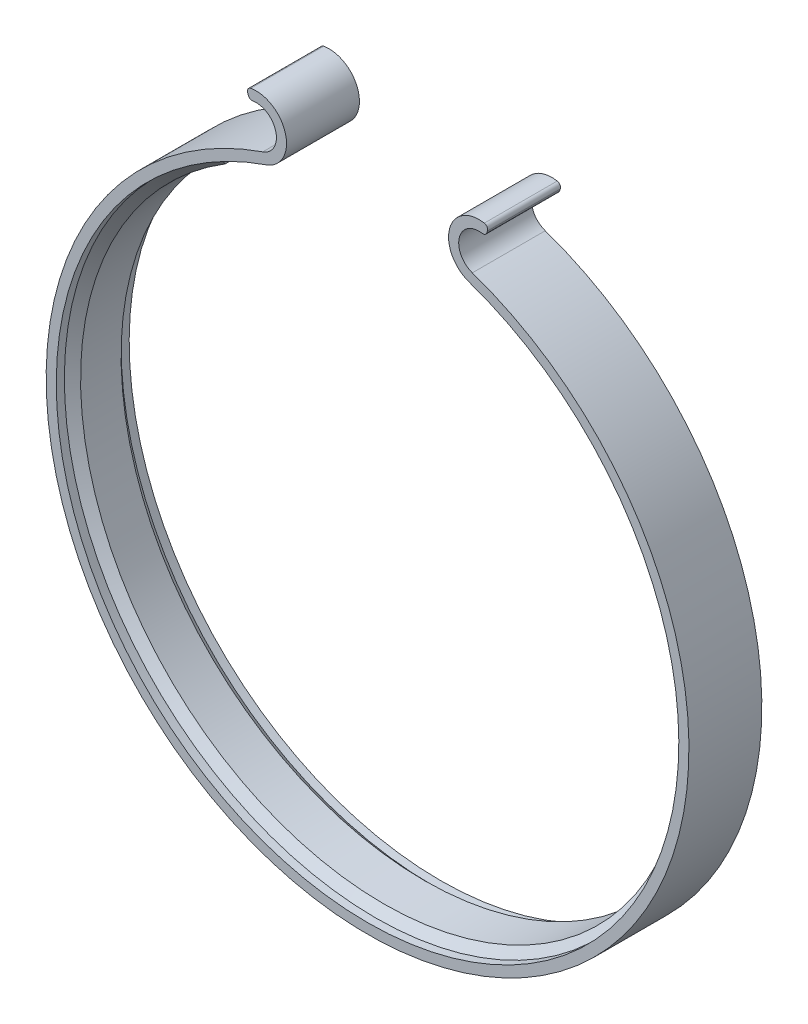
SolidWorks part; units mm, degrees
ref_plane "Front Plane" through (0, 0, 0) normal (0, 0, 1) x (1, 0, 0)
ref_plane "Top Plane" through (0, 0, 0) normal (0, 1, 0) x (1, 0, 0)
ref_plane "Right Plane" through (0, 0, 0) normal (1, 0, 0) x (0, 0, -1)
sketch "Sketch1" plane through (0, 0, 0) normal (0, 0, 1) x (1, 0, 0)
  line L0 (0, 0) -> (0, 98.4093) construction
  line L1 (29.4288, 85.3341) -> (29.5939, 85.813)
  line L3 (-29.4288, 85.3341) -> (-29.5939, 85.813)
  arc A0 (-25.0548, 72.6511) -> (25.0548, 72.6511) centre (0, 0) ccw
  arc A1 (-25.8699, 75.0145) -> (25.8699, 75.0145) centre (0, 0) ccw
  arc A2 (-25.8699, 75.0145) -> (-28.3195, 84.6737) centre (-27.5, 79.7413) ccw
  arc A3 (-25.0548, 72.6511) -> (-28.8253, 87.1233) centre (-27.5, 79.7413) ccw
  arc A4 (25.0548, 72.6511) -> (28.8253, 87.1233) centre (27.5, 79.7413) cw
  arc A5 (25.8699, 75.0145) -> (28.3195, 84.6737) centre (27.5, 79.7413) cw
  arc A6 (28.8253, 87.1233) -> (29.5939, 85.813) centre (28.6486, 86.139) cw
  arc A7 (28.3195, 84.6737) -> (29.4288, 85.3341) centre (28.4834, 85.6601) ccw
  arc A8 (-29.5939, 85.813) -> (-28.8253, 87.1233) centre (-28.6486, 86.139) cw
  arc A9 (-28.3195, 84.6737) -> (-29.4288, 85.3341) centre (-28.4834, 85.6601) cw
  point P10 (0, 0)
  point P11 (-24.1754, 72.9484)
  point P12 (0, 0)
  point P16 (-19.4193, 74.356)
  point P17 (-21.9041, 73.6623)
  point P18 (17.7307, 74.7766)
  dimension "D1" = 2.5
  dimension "D2" = 153.7
  dimension "D3" = 1
  dimension "10" = 10
  dimension "D4" = 55
extrude "Boss-Extrude1" add sketch "Sketch1" along normal blind 18
sketch "Sketch2" plane through (0, 0, 0) normal (1, 0, 0) x (0, 0, -1)
  line L1 (-15, -76.85) -> (-15, -70.6761) construction
  line L6 (-18, 72.6511) -> (-18, -76.85) construction
  line L7 (-14, -74.85) -> (-16, -76.85)
  line L8 (-16, -76.85) -> (-2, -76.85)
  line L9 (-14, -74.85) -> (-4, -74.85)
  line L10 (-18, -67.2275) -> (0, -67.2275) construction
  line L11 (0, -76.85) -> (0, 72.6511) construction
  line L12 (-9, -67.2275) -> (-9, -89.1861) construction
  line L13 (-4, -74.85) -> (-2, -76.85)
  line L14 (0, 0) -> (-38.791, 0) construction
  point P17 (-9, -74.85)
  point P18 (-9, -76.85)
  dimension "D1" = 45
  dimension "D2" = 3
  dimension "D3" = 2
  dimension "D4" = 1
  dimension "D5" = 76.85
revolve "Revolve1" add sketch "Sketch2" angle 150 about L14 other way angle 150
chamfer "Chamfer1" distance 2 angle 45 2 edges at (37.425, 64.822, 9) (-37.425, 64.822, 9)
